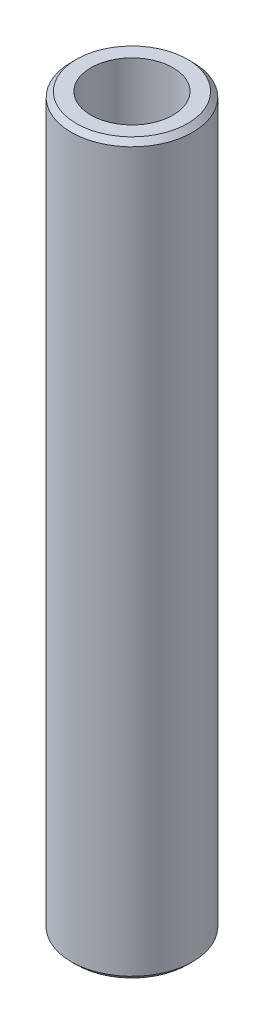
SolidWorks part; units mm, degrees
ref_plane "Front Plane" through (0, 0, 0) normal (0, 0, 1) x (1, 0, 0)
ref_plane "Top Plane" through (0, 0, 0) normal (0, 1, 0) x (1, 0, 0)
ref_plane "Right Plane" through (0, 0, 0) normal (1, 0, 0) x (0, 0, -1)
sketch "Sketch1" plane through (0, 0, 0) normal (0, 1, 0) x (1, 0, 0)
  circle A0 centre (0, 0) radius 50
  dimension "SHAFT_OD" = 100
extrude "Boss-Extrude1" add sketch "Sketch1" along normal blind 600
sketch "Sketch2" plane through (0, 0, 0) normal (0, 1, 0) x (1, 0, 0)
  circle A0 centre (0, 0) radius 33.8407
  dimension "BORE_D" = 67.6814
extrude "Cut-Extrude1" cut sketch "Sketch2" along normal through all
chamfer "Chamfer1" distance 4.1752 angle 45 2 edges at (0, 600, 50) (0, 0, 50)
